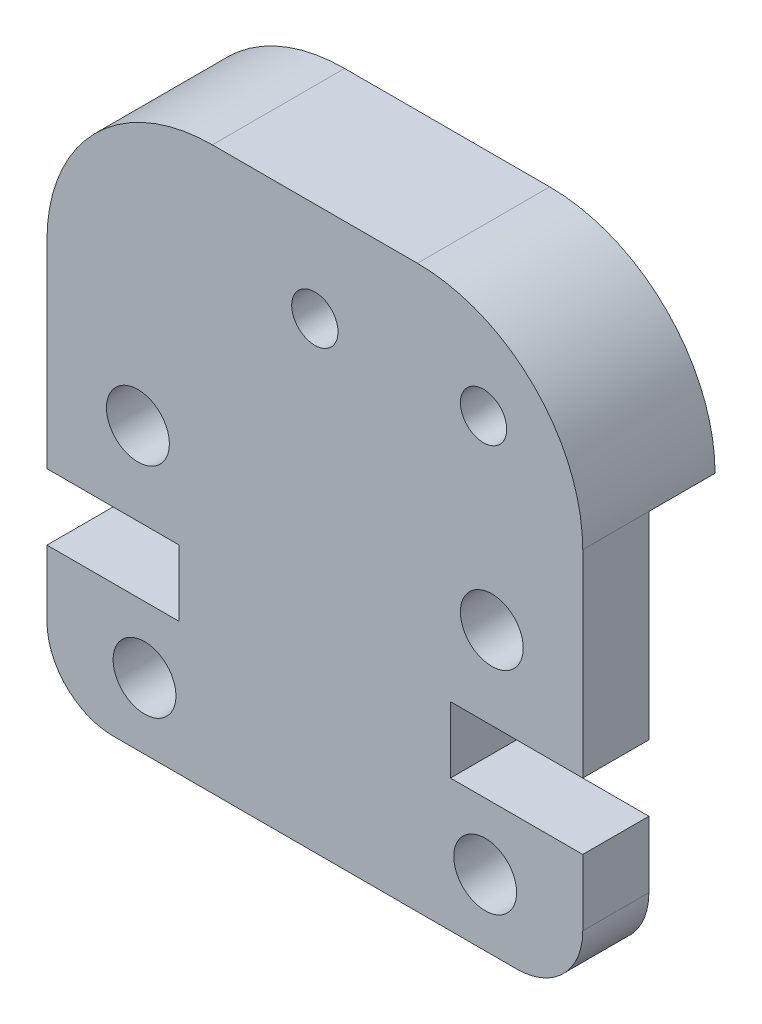
SolidWorks part; units mm, degrees
ref_plane "Front Plane" through (0, 0, 0) normal (0, 0, 1) x (1, 0, 0)
ref_plane "Top Plane" through (0, 0, 0) normal (0, 1, 0) x (1, 0, 0)
ref_plane "Right Plane" through (0, 0, 0) normal (1, 0, 0) x (0, 0, -1)
sketch "Sketch1" plane through (0, 0, 0) normal (0, 0, 1) x (1, 0, 0)
  line L0 (0, 16.98) -> (0, 0) construction
  line L1 (3.1, 16.98) -> (-3.1, 16.98)
  line L2 (6.1, 0) -> (-6.1, 0)
  line L3 (-8.1, 6) -> (-4.1, 6)
  line L4 (-4.1, 6) -> (-4.1, 4)
  line L5 (-4.1, 4) -> (-8.1, 4)
  line L6 (-8.1, 2) -> (-8.1, 4)
  line L7 (8.1, 11.98) -> (8.1, 6)
  line L8 (-8.1, 11.98) -> (-8.1, 6)
  line L9 (5.1, 13.98) -> (0, 13.98) construction
  line L24 (8.1, 2) -> (8.1, 4)
  line L27 (4.1, 4) -> (8.1, 4)
  line L30 (4.1, 6) -> (4.1, 4)
  line L31 (8.1, 6) -> (4.1, 6)
  circle A0 centre (-5.15, 2) radius 0.95
  circle A1 centre (-5.1, 13.98) radius 0.7 construction
  arc A2 (-8.1, 11.98) -> (-3.1, 16.98) centre (-3.1, 11.98) cw
  arc A3 (-6.1, 0) -> (-8.1, 2) centre (-6.1, 2) cw
  circle A4 centre (-5.35, 8.5) radius 0.95
  circle A5 centre (0, 13.98) radius 0.7
  circle A10 centre (5.35, 8.5) radius 0.95
  arc A12 (6.1, 0) -> (8.1, 2) centre (6.1, 2) ccw
  arc A14 (8.1, 11.98) -> (3.1, 16.98) centre (3.1, 11.98) ccw
  circle A16 centre (5.1, 13.98) radius 0.7
  circle A18 centre (5.15, 2) radius 0.95
  dimension "D1" = 1.9
  dimension "D2" = 1.4
  dimension "D3" = 16.98
  dimension "D4" = 2
  dimension "D5" = 5
  dimension "D6" = 6.1
  dimension "D7" = 3
  dimension "D8" = 3
  dimension "D9" = 2.75
  dimension "D10" = 8.5
extrude "Boss-Extrude1" add sketch "Sketch1" along normal blind 4
sketch "Sketch2" plane through (0, 0, 0) normal (0, 0, 1) x (1, 0, 0)
  line L0 (-8.1, 0) -> (8.1, 0)
  line L1 (8.1, 0) -> (8.1, 11.98)
  line L2 (8.1, 11.98) -> (-8.1, 11.98)
  line L3 (-8.1, 11.98) -> (-8.1, 0)
extrude "Cut-Extrude1" cut sketch "Sketch2" along normal blind 2
